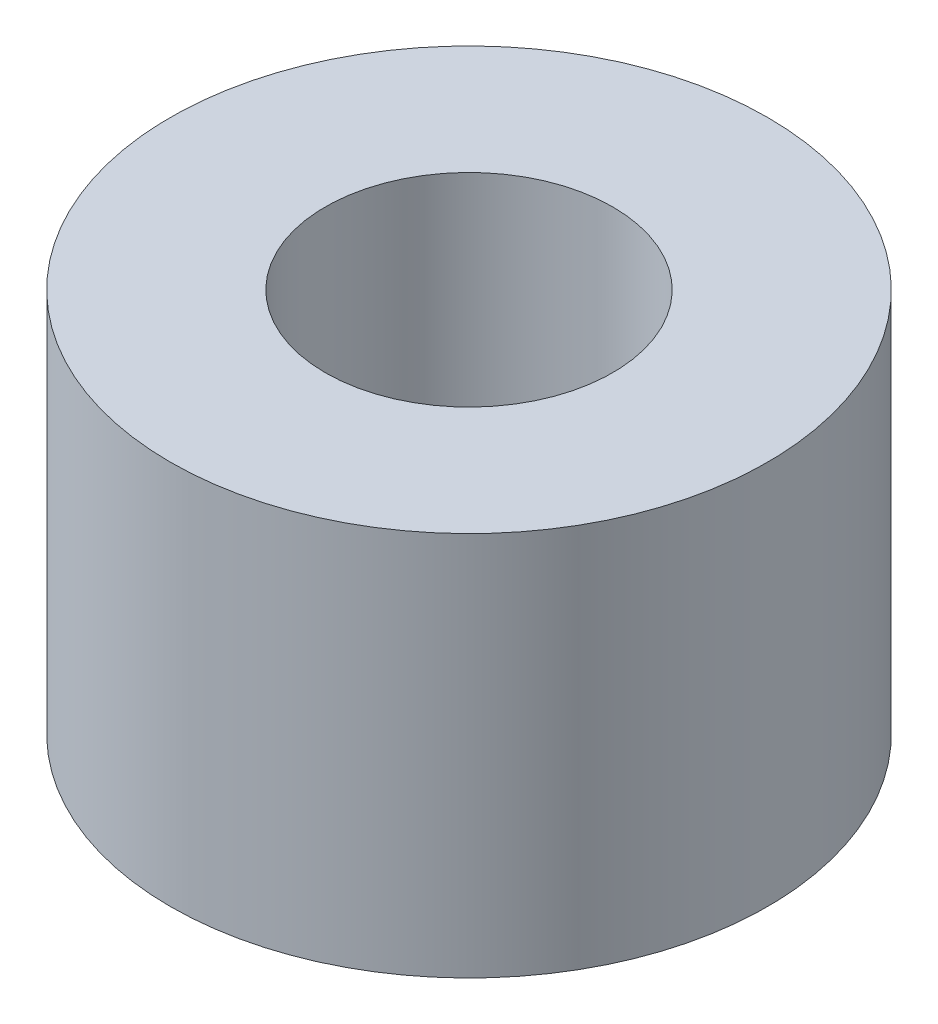
SolidWorks part; units mm, degrees
ref_plane "Front Plane" through (0, 0, 0) normal (0, 0, 1) x (1, 0, 0)
ref_plane "Top Plane" through (0, 0, 0) normal (0, 1, 0) x (1, 0, 0)
ref_plane "Right Plane" through (0, 0, 0) normal (1, 0, 0) x (0, 0, -1)
sketch "Sketch1" plane through (0, 0, 0) normal (0, 1, 0) x (1, 0, 0)
  circle A0 centre (0, 0) radius 2.75
  circle A1 centre (0, 0) radius 5.715
  dimension "D1" = 5.5
  dimension "D2" = 11.43
extrude "Boss-Extrude1" add sketch "Sketch1" along normal blind 7.366
